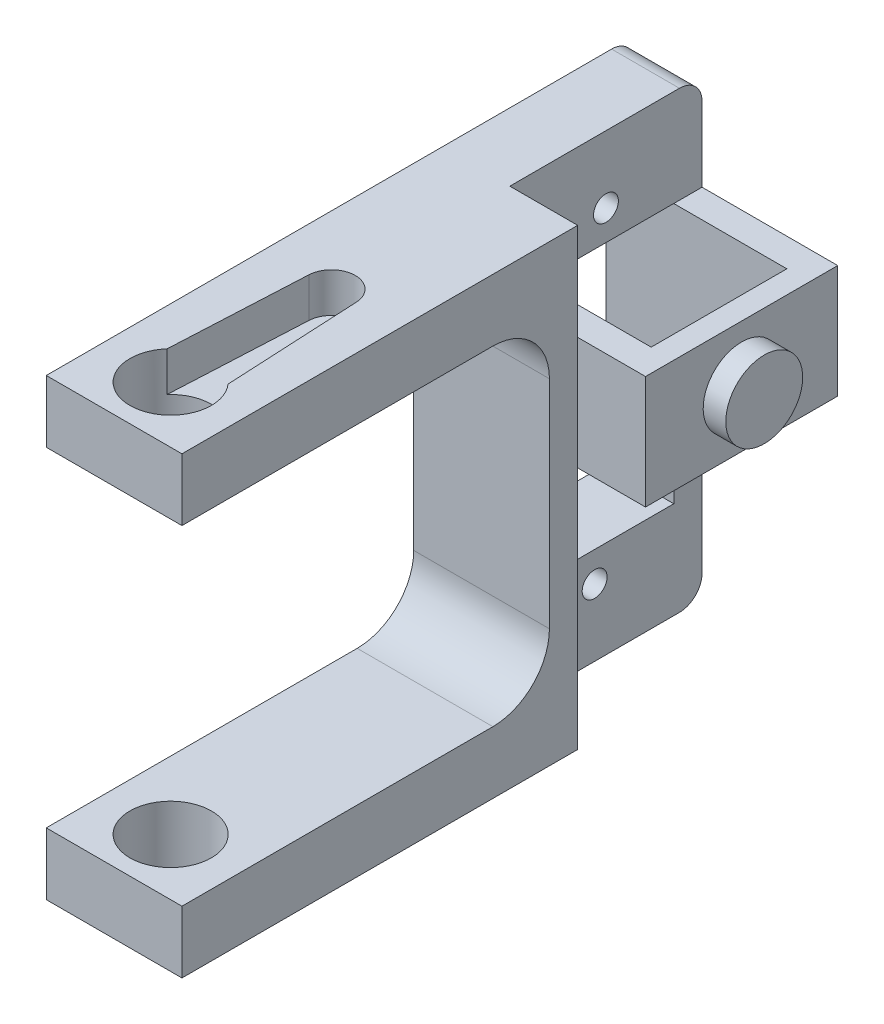
SolidWorks part; units mm, degrees
ref_plane "Front Plane" through (0, 0, 0) normal (0, 0, 1) x (1, 0, 0)
ref_plane "Top Plane" through (0, 0, 0) normal (0, 1, 0) x (1, 0, 0)
ref_plane "Right Plane" through (0, 0, 0) normal (1, 0, 0) x (0, 0, -1)
sketch "Sketch2" plane through (0, 0, 0) normal (0, 0, 1) x (1, 0, 0)
  line L1 (-8.6815, 5.0365) -> (3.3185, 5.0365)
  line L2 (-8.6815, 5.0365) -> (-8.6815, -35.1135)
  line L3 (-8.6815, -35.1135) -> (3.3185, -35.1135)
  line L4 (3.3185, 5.0365) -> (3.3185, -35.1135)
  line L13 (-8.6815, 5.0365) -> (3.3185, 5.0365)
  line L14 (-8.6815, 5.0365) -> (-8.6815, -0.4635)
  line L15 (-8.6815, -0.4635) -> (3.3185, -0.4635)
  line L16 (3.3185, 5.0365) -> (3.3185, -0.4635)
  line L21 (-8.6815, -35.1135) -> (3.3185, -35.1135)
  line L22 (-8.6815, -35.1135) -> (-8.6815, -29.6135)
  line L23 (-8.6815, -29.6135) -> (3.3185, -29.6135)
  line L24 (3.3185, -35.1135) -> (3.3185, -29.6135)
  dimension "D1" = 12
  dimension "D2" = 40.15
  dimension "D3" = 5.5
  dimension "D4" = 5.5
extrude "Boss-Extrude2" add sketch "Sketch2" along normal blind 35 contours L2 L15 L4 L1 | L22 L21 L24 L23 region at (-2.6815, 2.2865, 0)
extrude "Boss-Extrude3" add sketch "Sketch2<3>" along normal blind 2.5 contours L15 L2 L3 L4 region at (-2.6815, -15.0385, 0)
sketch "Sketch2<3>" plane through (0, 0, 0) normal (0, 0, 1) x (1, 0, 0) same geometry as "Sketch2"
sketch "Sketch7" plane through (0, 0, 0) normal (0, 0, -1) x (-1, 0, 0)
  line L5 (8.6815, -35.1135) -> (-3.3185, -35.1135) construction
  line L6 (8.6815, 5.0365) -> (2.6815, 5.0365)
  line L7 (8.6815, 5.0365) -> (8.6815, -35.1135)
  line L8 (8.6815, -35.1135) -> (2.6815, -35.1135)
  line L9 (2.6815, 5.0365) -> (2.6815, -35.1135)
extrude "Boss-Extrude4" add sketch "Sketch7" along normal blind 17
sketch "Sketch8" plane through (-2.6815, 0, 0) normal (1, 0, 0) x (0, 0, -1)
  line L0 (8.5, -3.5385) -> (8.5, 5.0365) construction
  line L1 (2.5, -3.5385) -> (14.5, -3.5385)
  line L2 (2.5, -3.5385) -> (2.5, -26.5385)
  line L3 (2.5, -26.5385) -> (14.5, -26.5385)
  line L4 (14.5, -3.5385) -> (14.5, -26.5385)
  line L5 (17, 5.0365) -> (0, 5.0365) construction
  line L6 (14.5, -15.0385) -> (17, -15.0385) construction
  line L7 (17, 5.0365) -> (17, -35.1135) construction
  circle A2 centre (8.5, -0.8885) radius 1.1
  circle A3 centre (7.5, -29.1885) radius 1.1
  dimension "D3" = 2.2
  dimension "D1" = 23
  dimension "D2" = 12
  dimension "D4" = 2.65
  dimension "D5" = 2.65
extrude "Cut-Extrude5" cut sketch "Sketch8" against normal up to next
sketch "Sketch9" plane through (0, 5.0365, 0) normal (0, 1, 0) x (1, 0, 0)
  line L0 (-0.5842, -15.6688) -> (0.0185, -27.6188)
  line L1 (-5.3815, -27.6188) -> (-4.7789, -15.6688)
  line L2 (-8.6815, -35) -> (3.3185, -35) construction
  line L3 (-2.6815, -30) -> (-2.6815, -35) construction
  arc A0 (-5.3815, -27.6188) -> (0.0185, -27.6188) centre (-2.6815, -30) ccw
  arc A1 (-0.5842, -15.6688) -> (-4.7789, -15.6688) centre (-2.6815, -15.7745) ccw
  dimension "D1" = 3.6
  dimension "D5" = 2.1
  dimension "D2" = 5
  dimension "D3" = 11.95
  dimension "D4" = 11.95
  dimension "D6" = 5.4
extrude "Cut-Extrude6" cut sketch "Sketch9" against normal blind 3.5
sketch "Sketch10" plane through (0, 5.0365, 0) normal (0, 1, 0) x (1, 0, 0)
  circle A0 centre (-2.6815, -30) radius 3.6
  dimension "D1" = 7.2
extrude "Cut-Extrude7" cut sketch "Sketch10" against normal through all
fillet "Fillet6" radius 5 1 edges at (-2.6815, -0.4635, 2.5)
fillet "Fillet7" radius 5 1 edges at (-2.6815, -29.6135, 2.5)
sketch "Sketch12" plane through (-2.6815, 0, 0) normal (1, 0, 0) x (0, 0, -1)
  line L0 (0, 5.0365) -> (0, -35.1135) construction
  line L1 (0, -3.5435) -> (2.5, -3.5435)
  line L2 (0, -3.5435) -> (0, -13.5435)
  line L3 (0, -13.5435) -> (2.5, -13.5435)
  line L4 (2.5, -3.5435) -> (2.5, -13.5435)
  line L5 (2.5, -3.5385) -> (2.5, -26.5385) construction
  line L6 (14.5, -26.5385) -> (14.5, -3.5385) construction
  line L7 (14.5, -3.5435) -> (17, -3.5435)
  line L8 (14.5, -3.5435) -> (14.5, -13.5435)
  line L9 (14.5, -13.5435) -> (17, -13.5435)
  line L10 (17, -3.5435) -> (17, -13.5435)
  line L11 (17, 5.0365) -> (17, -35.1135) construction
  line L14 (17, 5.0365) -> (0, 5.0365) construction
  dimension "D1" = 10
  dimension "D2" = 8.58
  dimension "D3" = 8.58
extrude "Boss-Extrude5" add sketch "Sketch12" along normal blind 10
sketch "Sketch13" plane through (7.3185, 0, 0) normal (1, 0, 0) x (0, 0, -1)
  line L1 (0, -3.5435) -> (17, -3.5435)
  line L2 (0, -3.5435) -> (0, -13.5435)
  line L3 (0, -13.5435) -> (17, -13.5435)
  line L4 (17, -3.5435) -> (17, -13.5435)
extrude "Boss-Extrude6" add sketch "Sketch13" along normal blind 2
sketch "Sketch14" plane through (9.3185, 0, 0) normal (1, 0, 0) x (0, 0, -1)
  line L0 (17, -3.5435) -> (0, -3.5435) construction
  line L3 (8.5, -8.5435) -> (8.5, -3.5435) construction
  line L4 (8.5, -8.5435) -> (17, -8.5435) construction
  line L5 (17, -13.5435) -> (17, -3.5435) construction
  circle A0 centre (8.5, -8.5435) radius 3.4
  dimension "D1" = 6.8
extrude "Boss-Extrude7" add sketch "Sketch14" along normal blind 2
fillet "Fillet8" radius 2 1 edges at (-5.6815, 5.0365, -17)
fillet "Fillet9" radius 2 1 edges at (-5.6815, -35.1135, -17)
